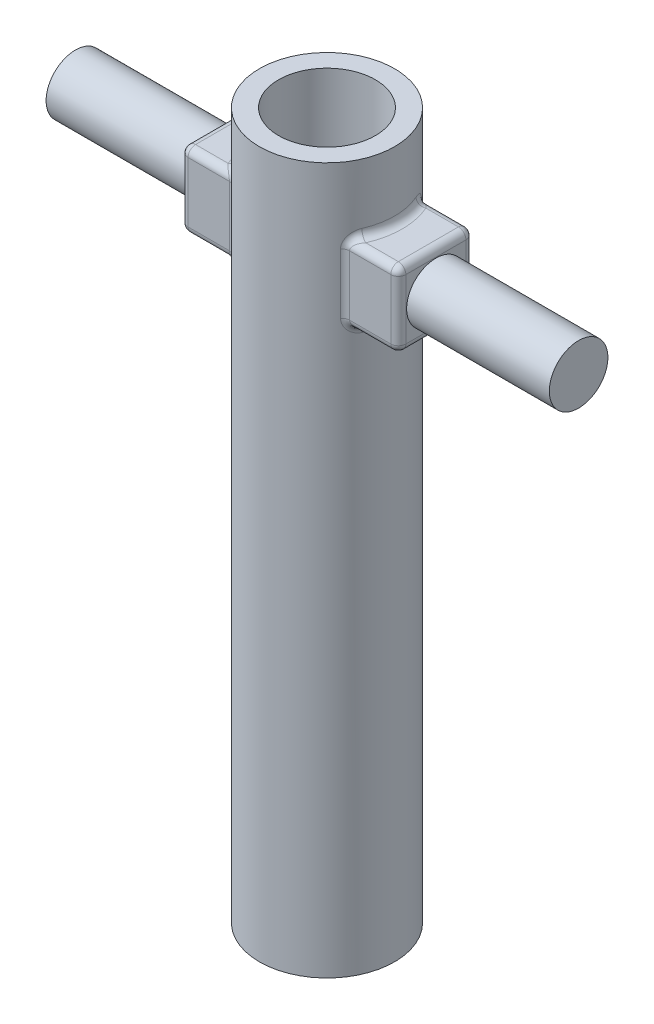
SolidWorks part; units mm, degrees
ref_plane "Front Plane" through (0, 0, 0) normal (0, 0, 1) x (1, 0, 0)
ref_plane "Top Plane" through (0, 0, 0) normal (0, 1, 0) x (1, 0, 0)
ref_plane "Right Plane" through (0, 0, 0) normal (1, 0, 0) x (0, 0, -1)
sketch "Sketch1" plane through (0, 0, 0) normal (0, 1, 0) x (1, 0, 0)
  circle A0 centre (0, 0) radius 3
  circle A1 centre (0, 0) radius 4.5
  dimension "D1" = 6
  dimension "D2" = 9
extrude "main_body" add sketch "Sketch1" along normal blind 20
ref_plane "Plane2" through (0, 40, 0) normal (0, -1, 0) x (-1, 0, 0)
sketch "Sketch2" plane through (0, 20, 0) normal (0, 1, 0) x (1, 0, 0)
  circle A0 centre (0, 0) radius 4.5
  dimension "D1" = 9
extrude "slider_shaft" add sketch "Sketch2" along normal blind 2
sketch "Sketch3" plane through (0, 22, 0) normal (0, 1, 0) x (1, 0, 0)
  circle A0 centre (0, 0) radius 3.225
  circle A1 centre (0, 0) radius 4.5
  dimension "D1" = 6.45
  dimension "D2" = 9
extrude "main_body2" add sketch "Sketch3" along normal blind 25
sketch "Sketch4" plane through (0, 40, 0) normal (0, 1, 0) x (1, 0, 0)
  line L1 (7.25, -2.5) -> (-7.25, -2.5)
  line L2 (7.25, -2.5) -> (7.25, 2.5)
  line L3 (7.25, 2.5) -> (-7.25, 2.5)
  line L4 (-7.25, -2.5) -> (-7.25, 2.5)
  circle A0 centre (0, 0) radius 3.225 construction
  circle A1 centre (0, 0) radius 4.5
  dimension "D5" = 9
  dimension "D1" = 14.5
  dimension "D2" = 7.25
  dimension "D3" = 5
  dimension "D4" = 2.5
extrude "axle_base" add sketch "Sketch4" along normal blind 2.5 and the other way blind 2.5 contours L1 A1 L3 L2 | L3 A1 L1 L4 region at (5.7449, 40, 0) region at (-5.7449, 40, 0)
sketch "Sketch8" plane through (7.25, 0, 0) normal (1, 0, 0) x (0, 0, -1)
  line L1 (-2.5, 42.5) -> (2.5, 42.5) construction
  line L2 (2.5, 37.5) -> (2.5, 42.5) construction
  circle A0 centre (0, 40) radius 1.95
  dimension "D1" = 3.9
  dimension "D2" = 2.5
  dimension "D3" = 2.5
extrude "dowel_mount" cut sketch "Sketch8" against normal blind 3.5
sketch "Sketch5" plane through (7.25, 0, 0) normal (1, 0, 0) x (0, 0, -1)
  line L1 (2.5, 37.5) -> (2.5, 42.5) construction
  line L2 (-2.5, 42.5) -> (2.5, 42.5) construction
  circle A0 centre (0, 40) radius 2
  dimension "D1" = 4
  dimension "D3" = 2.5
  dimension "D2" = 2.5
ref_plane "Plane1" through (0, 0, 0) normal (1, 0, 0) x (0, 0, -1)
sketch "Sketch7" plane through (0, 22, 0) normal (0, 1, 0) x (1, 0, 0)
  circle A0 centre (0, 0) radius 2.5
  dimension "D1" = 5
fillet "axle_base_fillet" radius 0.5 24 edges at (7.25, 37.5, 0) (4.5, 37.5, 0) (5.4958, 37.5, 2.5) (3.7417, 40, 2.5) (7.25, 40, 2.5) (4.5, 42.5, 0) (7.25, 42.5, 0) (5.4958, 42.5, 2.5) (5.4958, 37.5, -2.5) (7.25, 40, -2.5) (5.4958, 42.5, -2.5) (3.7417, 40, -2.5) (-7.25, 37.5, 0) (-4.5, 37.5, 0) (-7.25, 40, -2.5) (-5.4958, 37.5, -2.5) (-3.7417, 40, -2.5) (-3.7417, 40, 2.5) (-5.4958, 37.5, 2.5) (-7.25, 40, 2.5) (-4.5, 42.5, 0) (-5.4958, 42.5, 2.5) (-7.25, 42.5, 0) (-5.4958, 42.5, -2.5)
extrude "slider_shaft_cut" cut sketch "Sketch3<2>" against normal blind 2 flip side to cut
sketch "Sketch3<2>" plane through (0, 22, 0) normal (0, 1, 0) x (1, 0, 0) same geometry as "Sketch3"
mirror "Mirror1" about plane through (0, 0, 0) normal (1, 0, 0) of "dowel_mount"
sketch "Sketch9" plane through (-3.75, 0, 0) normal (-1, 0, 0) x (0, 0, 1)
  circle A0 centre (0, 40) radius 1.95
extrude "Boss-Extrude1" add sketch "Sketch9" along normal blind 13
sketch "Sketch10" plane through (3.75, 0, 0) normal (1, 0, 0) x (0, 0, -1)
  circle A0 centre (0, 40) radius 1.95
extrude "Boss-Extrude2" add sketch "Sketch10" along normal blind 13
